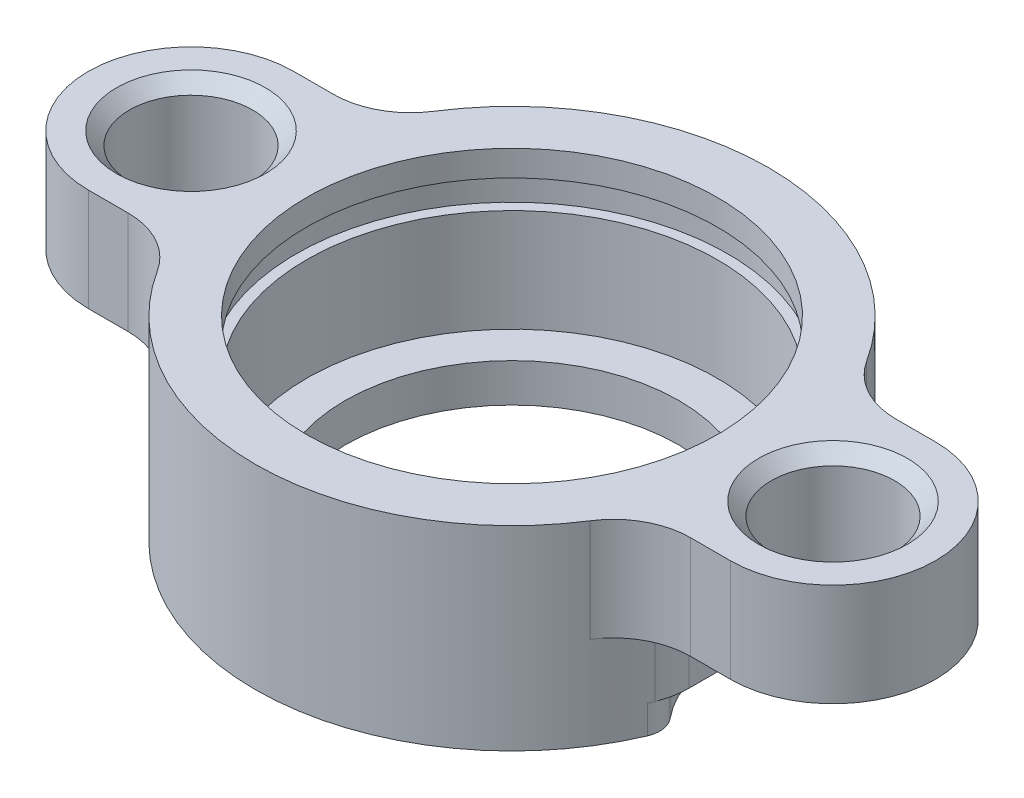
SolidWorks part; units mm, degrees
ref_plane "Plan de face" through (0, 0, 0) normal (0, 0, 1) x (1, 0, 0)
ref_plane "Plan de dessus" through (0, 0, 0) normal (0, 1, 0) x (1, 0, 0)
ref_plane "Plan de droite" through (0, 0, 0) normal (1, 0, 0) x (0, 0, -1)
sketch "Esquisse1" plane through (0, 0, 0) normal (0, 0, 1) x (1, 0, 0)
  line L0 (0, 6.6086) -> (0, -5.0424) construction
  line L1 (-6.5, -4) -> (-6.5, -5.5)
  line L2 (-6.5, -5.5) -> (-10, -5.5)
  line L3 (-10, -5.5) -> (-10, 2.1)
  line L4 (-10, 2.1) -> (-8, 2.1)
  line L5 (-8, 2.1) -> (-8, 1.1)
  line L6 (-8, 1.1) -> (-8.4, 1.1)
  line L7 (-8.4, 1.1) -> (-8.4, 0)
  line L8 (-8.4, 0) -> (-8, 0)
  line L9 (-8, 0) -> (-8, -4)
  line L10 (-8, -4) -> (-6.5, -4)
  dimension "D1" = 2
  dimension "D2" = 8
  dimension "D3" = 8.4
  dimension "D4" = 1.1
  dimension "D5" = 1.5
  dimension "D6" = 1.5
  dimension "D7" = 4
  dimension "D8" = 1
revolve "Révolution1" add sketch "Esquisse1" angle 360 about L0
sketch "Esquisse2" plane through (0, 2.1, 0) normal (0, 1, 0) x (1, 0, 0)
  line L0 (-12.5, -4) -> (-9.1652, -4)
  line L1 (-12.5, 4) -> (-9.1652, 4)
  line L2 (0, -4.18) -> (0, 4.18) construction
  line L5 (-9.5, -3.1225) -> (-9.5, 3.1225)
  circle A0 centre (-12.5, 0) radius 2.55 construction
  arc A1 (-12.5, 4) -> (-12.5, -4) centre (-12.5, 0) ccw
  circle A2 centre (0, 0) radius 10 construction
  arc A3 (-9.1652, 4) -> (-9.1652, -4) centre (0, 0) ccw
  circle A7 centre (-12.5, 0) radius 1.7 construction
  circle A11 centre (0, 0) radius 8 construction
  circle M6 centre (0, 0) radius 10
  dimension "D1" = 5.1
  dimension "D2" = 4
  dimension "D4" = 3.4
  dimension "D5" = 1.5
  dimension "D3" = 12.5
extrude "Boss.-Extru.1" add sketch "Esquisse2" against normal blind 4 contours L1 A1 L0 A0 M6 region at (-12.7463, 2.1, 0)
extrude "Enlèv. mat.-Extru.3" cut sketch "Esquisse2<6>" along normal up to surface (-4 mm away) from surface contours L5 M6 region at (-9.7004, 2.1, 0) up to face at (-12.0413, -1.9, 0) starting at face at (0, -5.5, 6.5)
sketch "Esquisse2<6>" plane through (0, 2.1, 0) normal (0, 1, 0) x (1, 0, 0) same geometry as "Esquisse2"
fillet "Congé2" radius 3 2 edges at (-9.5, -3.7, 3.1225) (-9.5, -3.7, -3.1225)
fillet "Congé3" radius 3 2 edges at (-9.1652, 0.1, -4) (-9.1652, 0.1, 4)
mirror "Symétrie1" about plane through (0, 0, 0) normal (1, 0, 0) of "Congé3", "Congé2", "Enlèv. mat.-Extru.3", "Boss.-Extru.1"
sketch "Esquisse8" plane through (0, 2.1, 0) normal (0, 1, 0) x (1, 0, 0)
  point P0 (-12.5, 0)
  point P3 (12.5, 0)
hole_wizard "Ø4.8 (4.8) Diameter Hole2" positions "Esquisse8" profile "Esquisse7" hole size "Ø4.8" standard "ANSI Metric"
sketch "Esquisse7" plane through (-12.5, 2.1, 0) normal (1, 0, 0) x (0, 0, 1)
  line L0 (0, 0) -> (0, 7.8421)
  line L1 (0, 7.8421) -> (2.4, 6.4)
  line L2 (2.4, 6.4) -> (2.4, 0)
  line L5 (2.4, 0) -> (0, 0)
  line L10 (0, 7.8421) -> (-2.4, 6.4) construction
  line L11 (0, -6.35) -> (0, 107.95) construction
  dimension "Hole Dia." = 4.8
  dimension "Hole Depth" = 6.4
  dimension "Drill Angle" = 118
chamfer "Chanfrein1" distance 0.5 angle 45 2 edges at (12.5, 2.1, 2.4) (-12.5, 2.1, 2.4)
sketch "Esquisse9" plane through (0, -5.5, 0) normal (0, -1, 0) x (1, 0, 0)
  circle A0 centre (-12.5, 0) radius 4.5
  circle A1 centre (12.5, 0) radius 4.5
  dimension "D1" = 9
extrude "Enlèv. mat.-Extru.4" cut sketch "Esquisse9" against normal blind 1.1
fillet "Congé4" radius 1 4 edges at (9.4211, -4.95, 3.2818) (9.4211, -4.95, -3.2818) (-9.4211, -4.95, 3.2818) (-9.4211, -4.95, -3.2818)
